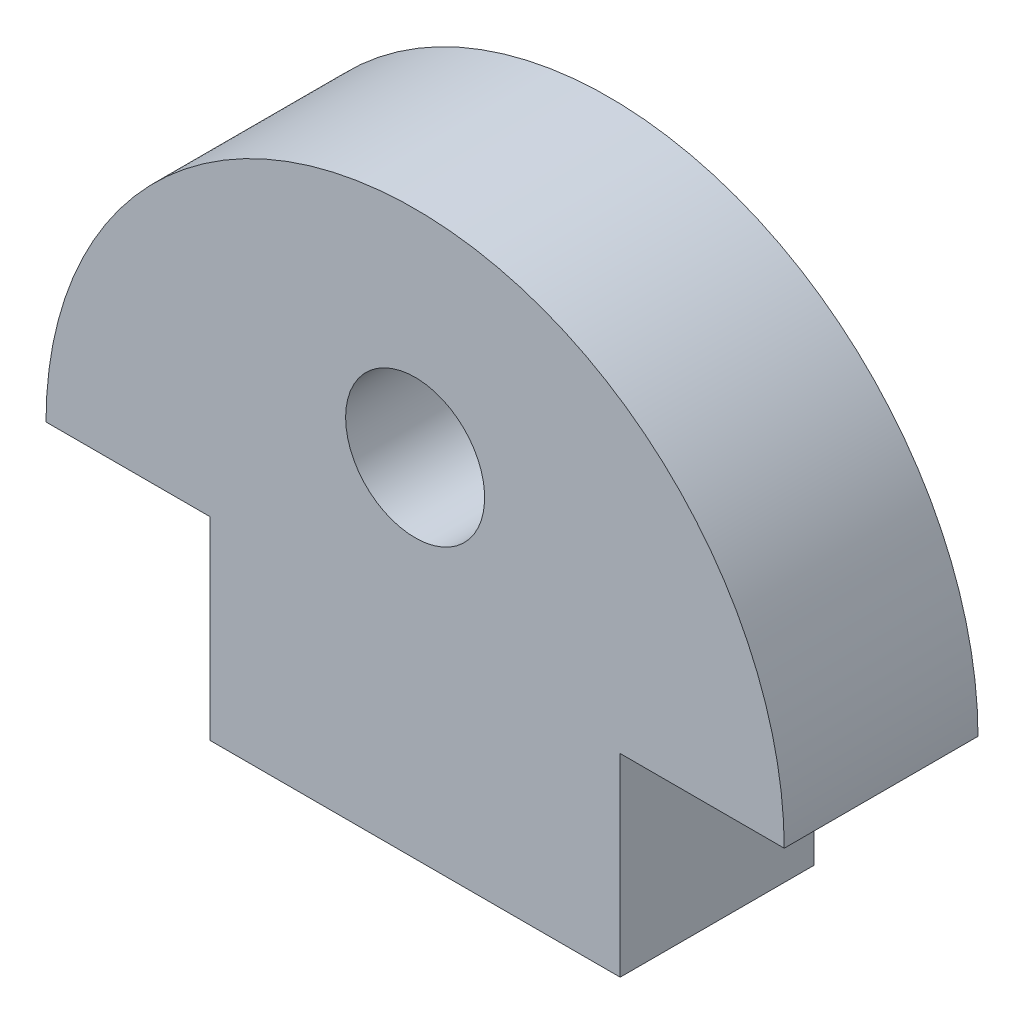
SolidWorks part; units mm, degrees
material "Custom Plastic"
ref_plane "Front Plane" through (0, 0, 0) normal (0, 0, 1) x (1, 0, 0)
ref_plane "Top Plane" through (0, 0, 0) normal (0, 1, 0) x (1, 0, 0)
ref_plane "Right Plane" through (0, 0, 0) normal (1, 0, 0) x (0, 0, -1)
sketch "Sketch1" plane through (0, 0, 0) normal (0, 0, 1) x (1, 0, 0)
  line L1 (-11.43, -12.7) -> (11.43, -12.7)
  line L2 (-11.43, -12.7) -> (-11.43, 12.7) construction
  line L3 (-11.43, 12.7) -> (11.43, 12.7) construction
  line L4 (11.43, -12.7) -> (11.43, 12.7) construction
  line L5 (-11.43, -12.7) -> (11.43, 12.7) construction
  line L6 (-11.43, 12.7) -> (11.43, -12.7) construction
  arc A0 (-11.43, -12.7) -> (11.43, -12.7) centre (0, -12.7) cw
  point P0 (0, 0)
  dimension "D1" = 22.86
  dimension "D2" = 25.4
extrude "Base" add sketch "Sketch1" along normal blind 6
sketch "Axle hole placement" plane through (0, 0, 6) normal (0, 0, 1) x (1, 0, 0)
  line L0 (-11.43, -7.9375) -> (11.43, -7.9375) construction
  line L3 (0, -1.27) -> (0, -12.7) construction
  line L4 (-11.43, -12.7) -> (11.43, -12.7) construction
  line L5 (-11.43, -12.7) -> (11.43, -12.7) construction
  line L7 (-11.43, -12.7) -> (11.43, -12.7) construction
  arc A0 (11.43, -12.7) -> (-11.43, -12.7) centre (0, -12.7) ccw construction
  point P12 (0, -7.9375)
  dimension "D1" = 4.7625
hole_wizard "Axle hole" positions "Sketch5" profile "Sketch4" hole size "#8" standard "ANSI Inch" end condition through all
sketch "Sketch5" plane through (0, 0, 0) normal (0, 0, -1) x (-1, 0, 0)
  point P3 (0, -7.9375)
sketch "Sketch4" plane through (0, -7.9375, 0) normal (1, 0, 0) x (0, 1, 0)
  line L0 (0, 0) -> (0, 6)
  line L1 (0, 6) -> (2.1526, 6)
  line L2 (2.1526, 6) -> (2.1526, 0)
  line L5 (2.1526, 0) -> (0, 0)
  line L11 (0, -6.35) -> (0, 107.95) construction
  dimension "Thru Hole Dia." = 4.3053
  dimension "Thru Hole Depth" = 6
sketch "Sketch8" plane through (0, 0, 6) normal (0, 0, 1) x (1, 0, 0)
  line L0 (-11.43, -12.7) -> (11.43, -12.7) construction
  line L1 (-6.35, -12.7) -> (6.35, -12.7)
  line L2 (-6.35, -12.7) -> (-6.35, -18.7)
  line L3 (-6.35, -18.7) -> (6.35, -18.7)
  line L4 (6.35, -12.7) -> (6.35, -18.7)
  point P6 (0, -12.7)
  dimension "D1" = 12.7
  dimension "D2" = 6
extrude "Boss-Extrude2" add sketch "Sketch8" against normal blind 6
equation "\"MAT_THICKNESS\"=0.23622"
equation "\"D1@Base\"=\"MAT_THICKNESS\""
equation "\"D2@Sketch8\"=\"MAT_THICKNESS\""
equation "\"D1@Boss-Extrude2\"=\"MAT_THICKNESS\""
